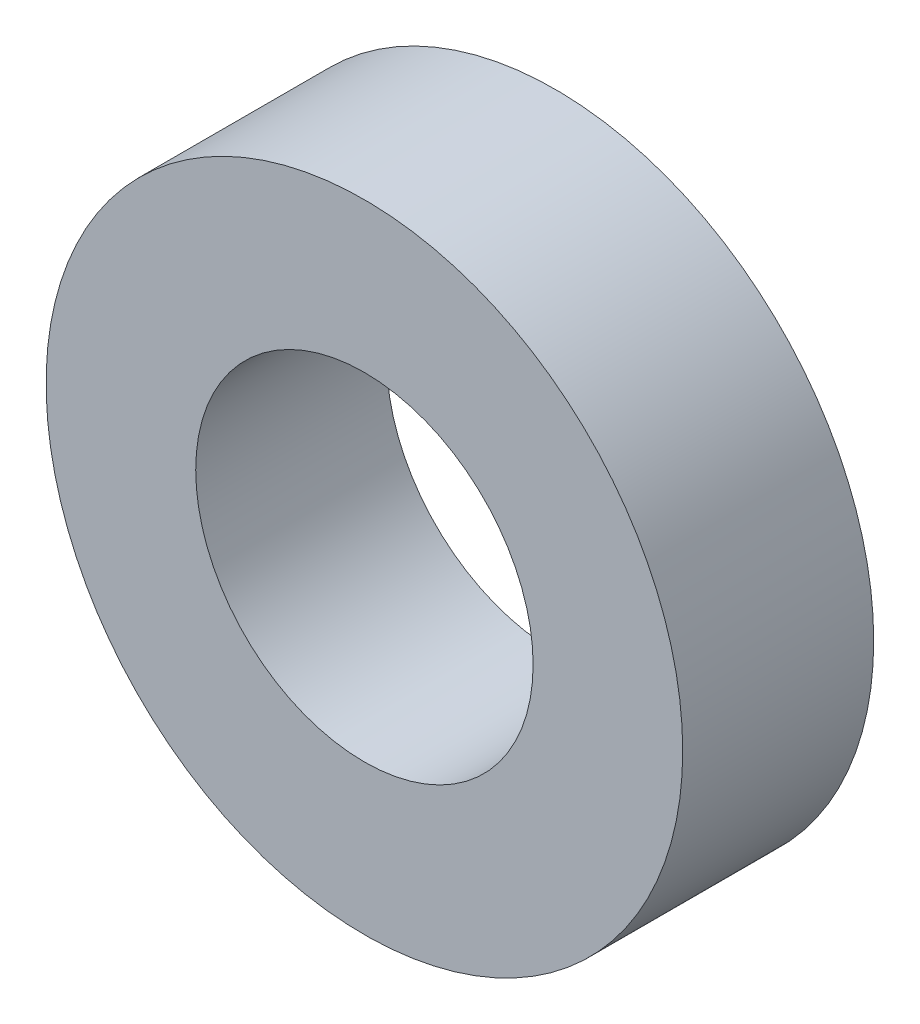
SolidWorks part; units mm, degrees
ref_plane "Front Plane" through (0, 0, 0) normal (0, 0, 1) x (1, 0, 0)
ref_plane "Top Plane" through (0, 0, 0) normal (0, 1, 0) x (1, 0, 0)
ref_plane "Right Plane" through (0, 0, 0) normal (1, 0, 0) x (0, 0, -1)
sketch "Sketch3" plane through (0, 0, 0) normal (0, 0, 1) x (1, 0, 0)
  circle A0 centre (0, 0) radius 2.65 construction
  circle A1 centre (0, 0) radius 5 construction
  point P6 (0, -2.65)
  dimension "OD" = 10
  dimension "ID" = 5.3
sketch "Sketch1" plane through (0, 0, 0) normal (1, 0, 0) x (0, 0, -1)
  line L0 (-1.5, -2.65) -> (-1.5, 2.65) construction
  line L1 (1.5, -5) -> (-1.5, -5) construction
  line L2 (1.5, -5) -> (1.5, 5) construction
  line L3 (1.5, 5) -> (-1.5, 5) construction
  line L4 (-1.5, -5) -> (-1.5, 5) construction
  line L5 (0, 5) -> (0, -5) construction
  line L6 (1.5, 0) -> (-1.5, 0) construction
  line L8 (0, 5) -> (0, -5) construction
  line L9 (-1.5, 2.65) -> (0, 2.65) construction
  point P0 (0, 0)
  point P7 (-1.5, 0)
  dimension "Length" = 3
sketch "Sketch2" plane through (0, 0, 0) normal (0, 0, 1) x (1, 0, 0)
  circle A0 centre (0, 0) radius 5
  circle A1 centre (0, 0) radius 2.65
extrude "Extrude1" add sketch "Sketch2" along normal up to vertex and the other way up to vertex up to point (0, -5, 1.5) other way up to point (0, 5, -1.5)
